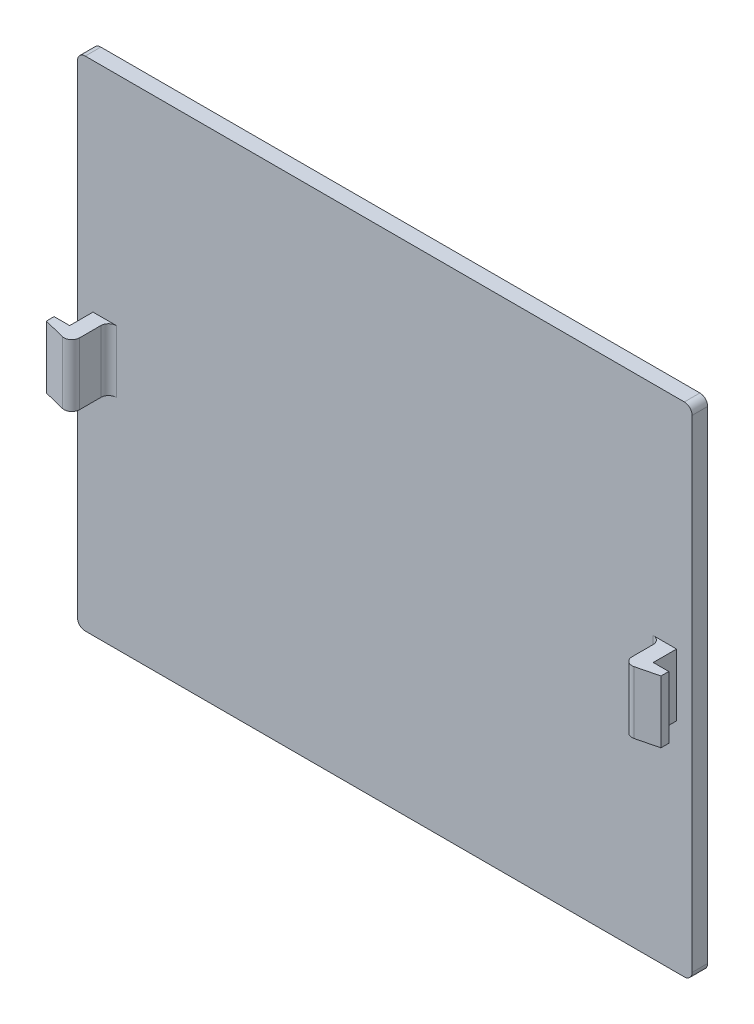
SolidWorks part; units mm, degrees
note: The reader was unsure of these and kept them because the rebuilt part matched: shared geometry of "基体<3>", "基体<4>".
ref_plane "前视基准面" through (0, 0, 0) normal (0, 0, 1) x (1, 0, 0)
ref_plane "上视基准面" through (0, 0, 0) normal (0, 1, 0) x (1, 0, 0)
ref_plane "右视基准面" through (0, 0, 0) normal (1, 0, 0) x (0, 0, -1)
other "Configuration Table"
sketch "基体" plane through (0, 0, 0) normal (0, 0, 1) x (1, 0, 0)
  line L0 (-38.7575, -28.3455) -> (-38.7575, 35.6545)
  line L1 (-36.7575, -26.3455) -> (38.2425, -26.3455)
  line L2 (-36.7575, -26.3455) -> (-36.7575, 33.6545)
  line L3 (-36.7575, 33.6545) -> (38.2425, 33.6545)
  line L4 (38.2425, -26.3455) -> (38.2425, 33.6545)
  line L5 (-36.7575, -26.3455) -> (38.2425, 33.6545) construction
  line L6 (-36.7575, 33.6545) -> (38.2425, -26.3455) construction
  line L7 (-38.7575, 35.6545) -> (40.2425, 35.6545)
  line L8 (40.2425, -28.3455) -> (40.2425, 35.6545)
  line L9 (-38.7575, -28.3455) -> (40.2425, -28.3455)
  line L10 (-38.7575, 3.6545) -> (-36.7575, 3.6545) construction
  line L11 (40.2425, 3.6545) -> (38.2425, 3.6545) construction
  line L12 (0.7425, 3.6545) -> (0.7425, 18.0853) construction
  line L13 (-38.7575, -0.3455) -> (-34.7575, -0.3455)
  line L14 (-38.7575, -0.3455) -> (-38.7575, 7.6545)
  line L15 (-38.7575, 7.6545) -> (-34.7575, 7.6545)
  line L16 (-34.7575, -0.3455) -> (-34.7575, 7.6545)
  line L17 (-38.7575, -0.3455) -> (-34.7575, 7.6545) construction
  line L18 (-38.7575, 7.6545) -> (-34.7575, -0.3455) construction
  line L19 (40.2425, 7.6545) -> (36.2425, 7.6545)
  line L20 (36.2425, -0.3455) -> (36.2425, 7.6545)
  line L21 (40.2425, -0.3455) -> (36.2425, -0.3455)
  line L22 (40.2425, -0.3455) -> (40.2425, 7.6545)
  point P0 (0.7425, 3.6545)
  dimension "D1" = 60
  dimension "D2" = 75
  dimension "D3" = 4
  dimension "D4" = 8
extrude "底部" add sketch "基体" along normal blind 2 contours L8 L21 L4 L1 L2 L13 L0 L9 | L15 L0 L13 L2 | L19 L8 L7 L0 L15 L2 L3 L4 | L13 L16 L15 L2 | L21 L4 L19 L20 | L21 L8 L19 L4 | L4 L21 L20 L19 L3 L2 L15 L16 L13 L1
extrude "扣柱" add sketch "基体<3>" along normal blind 3 from surface at 2 contours L13 L16 L15 L2 | L21 L4 L19 L20 starting at face at (0.7425, 3.6545, 2)
sketch "基体<3>" plane through (0, 0, 0) normal (0, 0, 1) x (1, 0, 0) same geometry as "基体"
extrude "扣子-1" add sketch "基体<4>" along normal blind 2 from surface at 5 contours L15 L0 L13 L2 | L13 L16 L15 L2 | L21 L4 L19 L20 | L21 L8 L19 L4 starting at face at (-35.7575, 3.6545, 5)
sketch "基体<4>" plane through (0, 0, 0) normal (0, 0, 1) x (1, 0, 0) same geometry as "基体"
sketch "草图3" plane through (0, 0, 0) normal (0, 1, 0) x (1, 0, 0)
  line L0 (-34.7575, -7) -> (-38.7575, -6)
  line L1 (-38.7575, -7) -> (-38.7575, -5) construction
  line L2 (-38.7575, -6) -> (-38.7575, -7)
  line L3 (-38.7575, -7) -> (-34.7575, -7)
  line L4 (36.2425, -7) -> (40.2425, -6)
  line L5 (40.2425, -7) -> (40.2425, -5) construction
  line L6 (40.2425, -6) -> (40.2425, -7)
  line L7 (40.2425, -7) -> (36.2425, -7)
extrude "切除-拉伸2" cut sketch "草图3" against normal through all both and the other way through all
fillet "边框圆角" radius 1 4 edges at (40.2425, -28.3455, 1) (40.2425, 35.6545, 1) (-38.7575, 35.6545, 1) (-38.7575, -28.3455, 1)
fillet "圆角4" radius 1 4 edges at (-34.7575, 3.6545, 7) (-34.7575, 3.6545, 2) (36.2425, 3.6545, 7) (36.2425, 3.6545, 2)
